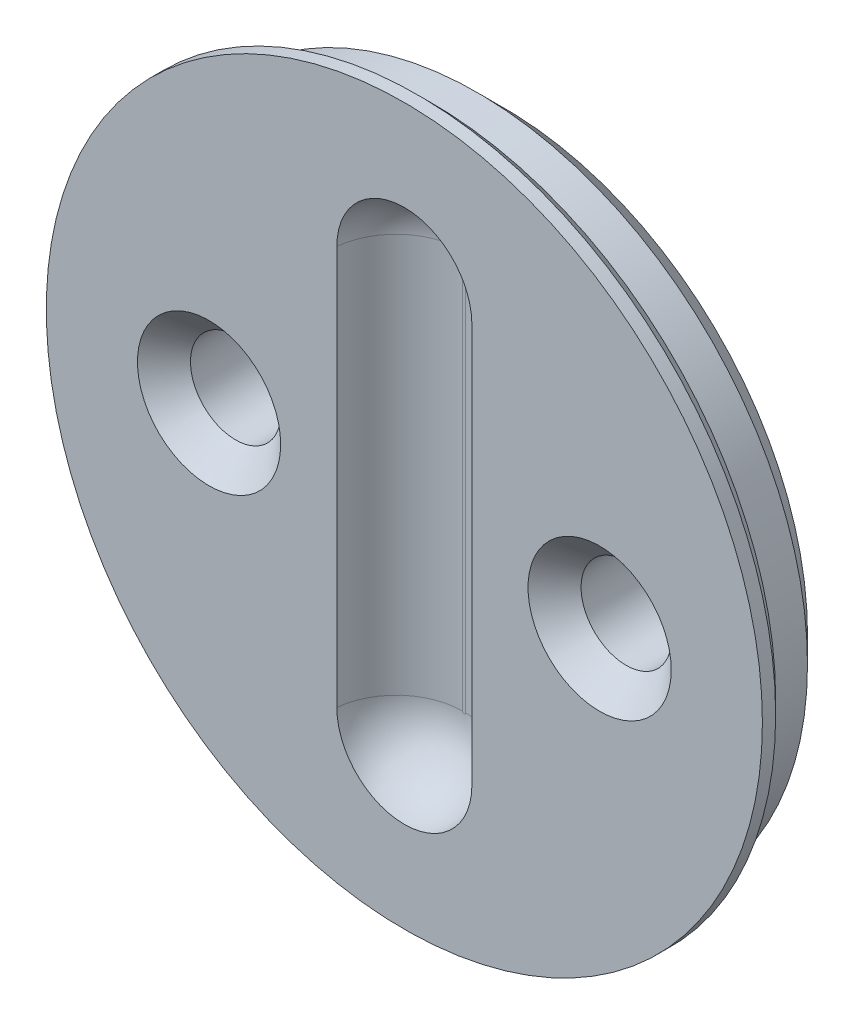
SolidWorks part; units mm, degrees
ref_plane "Front Plane" through (0, 0, 0) normal (0, 0, 1) x (1, 0, 0)
ref_plane "Top Plane" through (0, 0, 0) normal (0, 1, 0) x (1, 0, 0)
ref_plane "Right Plane" through (0, 0, 0) normal (1, 0, 0) x (0, 0, -1)
sketch "Sketch1" plane through (0, 0, 0) normal (0, 0, 1) x (1, 0, 0)
  line L0 (0, 9.3188) -> (0, -6.9028) construction
  circle A0 centre (0, 0) radius 12.45
  circle A1 centre (-7.363, 0) radius 1.7
  circle A2 centre (7.363, 0) radius 1.7
  dimension "D2" = 24.9
  dimension "D3" = 3.4
  dimension "D1" = 14.726
extrude "Boss-Extrude1" add sketch "Sketch1" against normal blind 2.75
sketch "Sketch2" plane through (0, 0, -2.75) normal (0, 0, -1) x (-1, 0, 0)
  line L1 (-3.85, 3.35) -> (3.85, 3.35)
  line L2 (-3.85, 3.35) -> (-3.85, -3.35)
  line L3 (-3.85, -3.35) -> (3.85, -3.35)
  line L4 (3.85, 3.35) -> (3.85, -3.35)
  line L5 (-3.85, 3.35) -> (3.85, -3.35) construction
  line L6 (-3.85, -3.35) -> (3.85, 3.35) construction
  point P0 (0, 0)
  dimension "D1" = 6.7
  dimension "D2" = 7.7
extrude "Boss-Extrude2" add sketch "Sketch2" along normal blind 3.5
sketch "Sketch3" plane through (0, 0, 0) normal (0, 0, 1) x (1, 0, 0)
  circle A0 centre (0, 0) radius 13.5
  circle A1 centre (-7.363, 0) radius 1.7
  circle A2 centre (7.363, 0) radius 1.7
  circle A3 centre (-7.363, 0) radius 1.7 construction
  dimension "D1" = 27
extrude "Boss-Extrude3" add sketch "Sketch3" along normal blind 1
chamfer "Chamfer1" distance 1 angle 45 5 edges at (0, 3.35, -6.25) (3.85, 0, -6.25) (0, -3.35, -6.25) (-3.85, 0, -6.25) (12.45, 0, -2.75)
chamfer "Chamfer2" distance 0.5 angle 45 1 edges at (13.5, 0, 0)
sketch "Sketch4" plane through (0, 0, 1) normal (0, 0, 1) x (1, 0, 0)
  line L0 (0, 7.5257) -> (0, -7.5257) construction
  line L1 (2.5463, 7.5257) -> (2.5463, -7.5257)
  line L2 (-2.5463, 7.5257) -> (-2.5463, -7.5257)
  arc A0 (2.5463, 7.5257) -> (-2.5463, 7.5257) centre (0, 7.5257) ccw
  arc A1 (-2.5463, -7.5257) -> (2.5463, -7.5257) centre (0, -7.5257) ccw
  point P2 (0, 0)
extrude "Cut-Extrude1" cut sketch "Sketch4" against normal blind 2.25
fillet "Fillet1" radius 2.5 4 edges at (-2.5463, 0, -1.25) (2.5463, 0, -1.25) (0, 10.0719, -1.25) (0, -10.0719, -1.25)
chamfer "Chamfer3" distance 1 angle 45 2 edges at (9.063, 0, 1) (-5.663, 0, 1)
